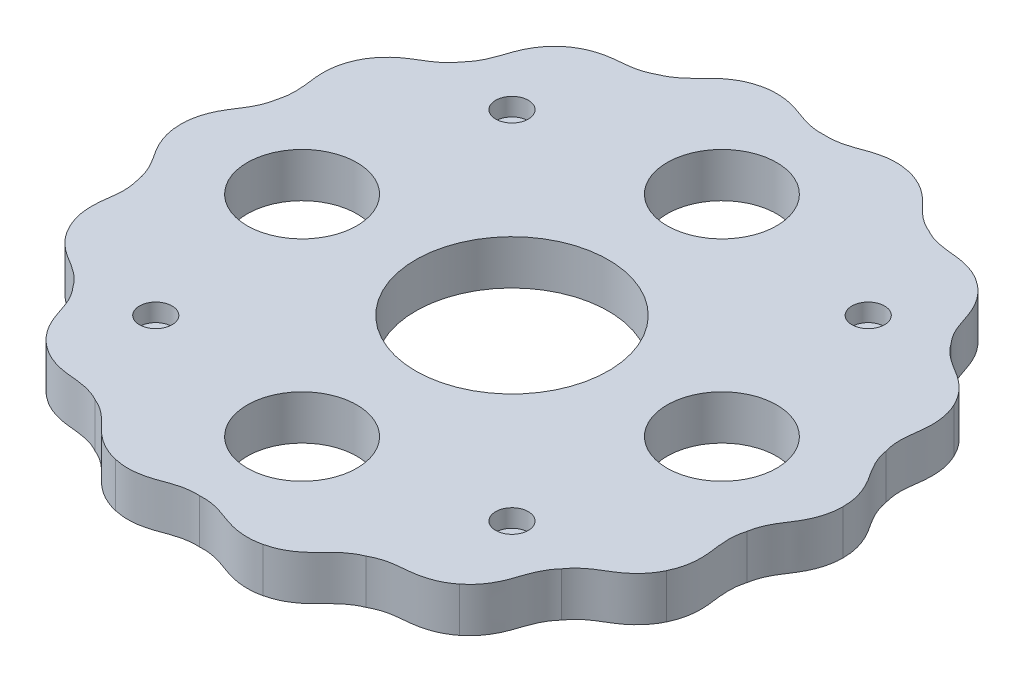
SolidWorks part; units mm, degrees
ref_plane "Front Plane" through (0, 0, 0) normal (0, 0, 1) x (1, 0, 0)
ref_plane "Top Plane" through (0, 0, 0) normal (0, 1, 0) x (1, 0, 0)
ref_plane "Right Plane" through (0, 0, 0) normal (1, 0, 0) x (0, 0, -1)
sketch "Sketch1" plane through (0, 0, 0) normal (0, 1, 0) x (1, 0, 0)
  line L0 (0, 0) -> (37.5, 0) construction
  line L1 (0, 0) -> (37.4807, 1.2019) construction
  line L2 (0, 0) -> (37.423, 2.4026) construction
  line L3 (0, 0) -> (37.3267, 3.6009) construction
  line L4 (0, 0) -> (37.1921, 4.7954) construction
  line L5 (0, 0) -> (37.0193, 5.985) construction
  line L6 (0, 0) -> (36.8085, 7.1684) construction
  line L7 (0, 0) -> (36.5598, 8.3445) construction
  line L8 (0, 0) -> (36.2736, 9.512) construction
  line L9 (0, 0) -> (35.95, 10.6698) construction
  line L10 (0, 0) -> (35.5896, 11.8166) construction
  line L11 (0, 0) -> (35.1926, 12.9512) construction
  line L12 (0, 0) -> (34.7594, 14.0725) construction
  line L13 (0, 0) -> (34.2905, 15.1794) construction
  line L14 (0, 0) -> (33.7863, 16.2706) construction
  line L15 (37.5, 0) -> (38.5, 0) construction
  line L16 (37.4807, 1.2019) -> (38.3521, 1.6927) construction
  line L17 (37.423, 2.4026) -> (37.9413, 3.2578) construction
  line L18 (37.3267, 3.6009) -> (37.3588, 4.6003) construction
  line L19 (37.1921, 4.7954) -> (36.7296, 5.682) construction
  line L20 (37.0193, 5.985) -> (36.1812, 6.5305) construction
  line L21 (36.8085, 7.1684) -> (35.8105, 7.2325) construction
  line L22 (36.5598, 8.3445) -> (35.5849, 8.122) construction
  line L23 (37, 0.0019) -> (37, 0)
  line L24 (33.3367, 16.052) -> (33.3358, 16.0537)
  line L25 (37, -0.0019) -> (37, 0)
  line L26 (33.3367, -16.052) -> (33.3358, -16.0537)
  line L27 (33.335, -16.0554) -> (33.3358, -16.0537)
  line L28 (23.0706, -28.9266) -> (23.0691, -28.9278)
  line L29 (23.0677, -28.9289) -> (23.0691, -28.9278)
  line L30 (8.2351, -36.0719) -> (8.2333, -36.0723)
  line L31 (8.2315, -36.0727) -> (8.2333, -36.0723)
  line L32 (-8.2315, -36.0727) -> (-8.2333, -36.0723)
  line L33 (-8.2351, -36.0719) -> (-8.2333, -36.0723)
  line L34 (-23.0677, -28.9289) -> (-23.0691, -28.9278)
  line L35 (-23.0706, -28.9266) -> (-23.0691, -28.9278)
  line L36 (-33.335, -16.0554) -> (-33.3358, -16.0537)
  line L37 (-33.3367, -16.052) -> (-33.3358, -16.0537)
  line L38 (-37, -0.0019) -> (-37, 0)
  line L39 (-37, 0.0019) -> (-37, 0)
  line L40 (-33.3367, 16.052) -> (-33.3358, 16.0537)
  line L41 (-33.335, 16.0554) -> (-33.3358, 16.0537)
  line L42 (-23.0706, 28.9266) -> (-23.0691, 28.9278)
  line L43 (-23.0677, 28.9289) -> (-23.0691, 28.9278)
  line L44 (-8.2351, 36.0719) -> (-8.2333, 36.0723)
  line L45 (-8.2315, 36.0727) -> (-8.2333, 36.0723)
  line L46 (8.2315, 36.0727) -> (8.2333, 36.0723)
  line L47 (8.2351, 36.0719) -> (8.2333, 36.0723)
  line L48 (23.0677, 28.9289) -> (23.0691, 28.9278)
  line L49 (23.0706, 28.9266) -> (23.0691, 28.9278)
  line L50 (33.335, 16.0554) -> (33.3358, 16.0537)
  line L51 (35.5, 0.0037) -> (35.5, 0)
  line L52 (31.986, 15.3995) -> (31.9844, 15.4029)
  line L53 (35.5, -0.0037) -> (35.5, 0)
  line L54 (31.986, -15.3995) -> (31.9844, -15.4029)
  line L55 (31.9828, -15.4062) -> (31.9844, -15.4029)
  line L56 (22.1368, -27.7527) -> (22.1339, -27.755)
  line L57 (22.131, -27.7573) -> (22.1339, -27.755)
  line L58 (7.9031, -34.6091) -> (7.8995, -34.6099)
  line L59 (7.8959, -34.6108) -> (7.8995, -34.6099)
  line L60 (-7.8959, -34.6108) -> (-7.8995, -34.6099)
  line L61 (-7.9031, -34.6091) -> (-7.8995, -34.6099)
  line L62 (-22.131, -27.7573) -> (-22.1339, -27.755)
  line L63 (-22.1368, -27.7527) -> (-22.1339, -27.755)
  line L64 (-31.9828, -15.4062) -> (-31.9844, -15.4029)
  line L65 (-31.986, -15.3995) -> (-31.9844, -15.4029)
  line L66 (-35.5, -0.0037) -> (-35.5, 0)
  line L67 (-35.5, 0.0037) -> (-35.5, 0)
  line L68 (-31.986, 15.3995) -> (-31.9844, 15.4029)
  line L69 (-31.9828, 15.4062) -> (-31.9844, 15.4029)
  line L70 (-22.1368, 27.7527) -> (-22.1339, 27.755)
  line L71 (-22.131, 27.7573) -> (-22.1339, 27.755)
  line L72 (-7.9031, 34.6091) -> (-7.8995, 34.6099)
  line L73 (-7.8959, 34.6108) -> (-7.8995, 34.6099)
  line L74 (7.8959, 34.6108) -> (7.8995, 34.6099)
  line L75 (7.9031, 34.6091) -> (7.8995, 34.6099)
  line L76 (22.131, 27.7573) -> (22.1339, 27.755)
  line L77 (22.1368, 27.7527) -> (22.1339, 27.755)
  line L78 (31.9828, 15.4062) -> (31.9844, 15.4029)
  circle A0 centre (0, 0) radius 35 construction
  circle A1 centre (37.5, 0) radius 2.5 construction
  circle A2 centre (0, 0) radius 37.5 construction
  spline S0 degree 3 poles (35.5849, 8.122) (35.6266, 7.5364) (36.0345, 6.7125) (36.7836, 5.6218) (37.4152, 4.5501) (38.2239, 2.702) (38.5014, 1.1074) (38.5, 0) knots 0 0 0 0 0.195516 0.310928 0.453873 0.621058 1 1 1 1
  spline S1 degree 3 poles (35.5849, 8.122) (35.3683, 8.6678) (35.3784, 9.5871) (35.5801, 10.8948) (35.6841, 12.1344) (35.611, 14.1503) (35.169, 15.7074) (34.6873, 16.7045) knots 0 0 0 0 0.195516 0.310928 0.453873 0.621058 1 1 1 1
  spline S2 degree 1 poles (34.1119, 7.7858) (33.3367, 16.052) knots 0 0 1 1 construction
  spline S3 degree 1 poles (34.1119, 7.7858) (37, 0.0019) knots 0 0 1 1 construction
  spline S4 degree 3 poles (33.3367, 16.052) (33.6005, 15.5058) (33.9037, 14.6401) (34.1146, 13.4372) (34.174, 12.5211) (34.1413, 11.5771) (34.0239, 10.6392) (33.8823, 9.6155) (33.9055, 8.625) (34.0243, 8.0514) (34.1119, 7.7858) knots 0.015853 0.015853 0.015853 0.015853 0.26189 0.384908 0.507927 0.630945 0.753963 0.876982 0.938491 1 1 1 1
  spline S5 degree 3 poles (34.1119, 7.7858) (34.1483, 7.5085) (34.2901, 6.9402) (34.6989, 6.0377) (35.2706, 5.1769) (35.7834, 4.3828) (36.2224, 3.5464) (36.5664, 2.6953) (36.8983, 1.52) (37.0008, 0.6085) (37, 0.0019) knots 0.015853 0.015853 0.015853 0.015853 0.077362 0.138872 0.26189 0.384908 0.507927 0.630945 0.753963 1 1 1 1
  spline S6 degree 3 poles (37, -0.0019) (37.0008, -0.6085) (36.8983, -1.52) (36.5664, -2.6953) (36.2224, -3.5464) (35.7834, -4.3828) (35.2706, -5.1769) (34.6989, -6.0377) (34.2901, -6.9402) (34.1483, -7.5085) (34.1119, -7.7858) knots 0.015853 0.015853 0.015853 0.015853 0.26189 0.384908 0.507927 0.630945 0.753963 0.876982 0.938491 1 1 1 1
  spline S7 degree 3 poles (34.1119, -7.7858) (34.0243, -8.0514) (33.9055, -8.625) (33.8823, -9.6155) (34.0239, -10.6392) (34.1413, -11.5771) (34.174, -12.5211) (34.1146, -13.4372) (33.9037, -14.6401) (33.6005, -15.5058) (33.3367, -16.052) knots 0.015853 0.015853 0.015853 0.015853 0.077362 0.138872 0.26189 0.384908 0.507927 0.630945 0.753963 1 1 1 1
  spline S8 degree 3 poles (33.335, -16.0554) (33.0725, -16.6022) (32.5847, -17.3791) (31.7758, -18.2939) (31.0965, -18.9115) (30.3381, -19.4746) (29.5316, -19.9675) (28.6429, -20.4951) (27.8831, -21.1308) (27.5087, -21.5813) (27.3556, -21.8154) knots 0.015853 0.015853 0.015853 0.015853 0.26189 0.384908 0.507927 0.630945 0.753963 0.876982 0.938491 1 1 1 1
  spline S9 degree 3 poles (27.3556, -21.8154) (27.1615, -22.0167) (26.8056, -22.4819) (26.3549, -23.3642) (26.0383, -24.348) (25.7371, -25.2439) (25.357, -26.1087) (24.906, -26.9083) (24.1941, -27.9005) (23.5453, -28.549) (23.0706, -28.9266) knots 0.015853 0.015853 0.015853 0.015853 0.077362 0.138872 0.26189 0.384908 0.507927 0.630945 0.753963 1 1 1 1
  spline S10 degree 3 poles (23.0677, -28.9289) (22.5939, -29.3077) (21.8173, -29.796) (20.6915, -30.2693) (19.8116, -30.531) (18.884, -30.7092) (17.9435, -30.8034) (16.9139, -30.8931) (15.9535, -31.1362) (15.4207, -31.3797) (15.1812, -31.5241) knots 0.015853 0.015853 0.015853 0.015853 0.26189 0.384908 0.507927 0.630945 0.753963 0.876982 0.938491 1 1 1 1
  spline S11 degree 3 poles (15.1812, -31.5241) (14.919, -31.6213) (14.3964, -31.886) (13.6076, -32.4854) (12.8955, -33.2344) (12.2354, -33.9109) (11.5177, -34.5251) (10.7645, -35.0499) (9.6926, -35.6349) (8.8266, -35.9377) (8.2351, -36.0719) knots 0.015853 0.015853 0.015853 0.015853 0.077362 0.138872 0.26189 0.384908 0.507927 0.630945 0.753963 1 1 1 1
  spline S12 degree 3 poles (8.2315, -36.0727) (7.6402, -36.2085) (6.7287, -36.3114) (5.5091, -36.2494) (4.6028, -36.1034) (3.6897, -35.8614) (2.8014, -35.5383) (1.8349, -35.1724) (0.8641, -34.9747) (0.2785, -34.9629) (0, -34.9891) knots 0.015853 0.015853 0.015853 0.015853 0.26189 0.384908 0.507927 0.630945 0.753963 0.876982 0.938491 1 1 1 1
  spline S13 degree 3 poles (0, -34.9891) (-0.2785, -34.9629) (-0.8641, -34.9747) (-1.8349, -35.1724) (-2.8014, -35.5383) (-3.6897, -35.8614) (-4.6028, -36.1034) (-5.5091, -36.2494) (-6.7287, -36.3114) (-7.6402, -36.2085) (-8.2315, -36.0727) knots 0.015853 0.015853 0.015853 0.015853 0.077362 0.138872 0.26189 0.384908 0.507927 0.630945 0.753963 1 1 1 1
  spline S14 degree 3 poles (-8.2351, -36.0719) (-8.8266, -35.9377) (-9.6926, -35.6349) (-10.7645, -35.0499) (-11.5177, -34.5251) (-12.2354, -33.9109) (-12.8955, -33.2344) (-13.6076, -32.4854) (-14.3964, -31.886) (-14.919, -31.6213) (-15.1812, -31.5241) knots 0.015853 0.015853 0.015853 0.015853 0.26189 0.384908 0.507927 0.630945 0.753963 0.876982 0.938491 1 1 1 1
  spline S15 degree 3 poles (-15.1812, -31.5241) (-15.4207, -31.3797) (-15.9535, -31.1362) (-16.9139, -30.8931) (-17.9435, -30.8034) (-18.884, -30.7092) (-19.8116, -30.531) (-20.6915, -30.2693) (-21.8173, -29.796) (-22.5939, -29.3077) (-23.0677, -28.9289) knots 0.015853 0.015853 0.015853 0.015853 0.077362 0.138872 0.26189 0.384908 0.507927 0.630945 0.753963 1 1 1 1
  spline S16 degree 3 poles (-23.0706, -28.9266) (-23.5453, -28.549) (-24.1941, -27.9005) (-24.906, -26.9083) (-25.357, -26.1087) (-25.7371, -25.2439) (-26.0383, -24.348) (-26.3549, -23.3642) (-26.8056, -22.4819) (-27.1615, -22.0167) (-27.3556, -21.8154) knots 0.015853 0.015853 0.015853 0.015853 0.26189 0.384908 0.507927 0.630945 0.753963 0.876982 0.938491 1 1 1 1
  spline S17 degree 3 poles (-27.3556, -21.8154) (-27.5087, -21.5813) (-27.8831, -21.1308) (-28.6429, -20.4951) (-29.5316, -19.9675) (-30.3381, -19.4746) (-31.0965, -18.9115) (-31.7758, -18.2939) (-32.5847, -17.3791) (-33.0725, -16.6022) (-33.335, -16.0554) knots 0.015853 0.015853 0.015853 0.015853 0.077362 0.138872 0.26189 0.384908 0.507927 0.630945 0.753963 1 1 1 1
  spline S18 degree 3 poles (-33.3367, -16.052) (-33.6005, -15.5058) (-33.9037, -14.6401) (-34.1146, -13.4372) (-34.174, -12.5211) (-34.1413, -11.5771) (-34.0239, -10.6392) (-33.8823, -9.6155) (-33.9055, -8.625) (-34.0243, -8.0514) (-34.1119, -7.7858) knots 0.015853 0.015853 0.015853 0.015853 0.26189 0.384908 0.507927 0.630945 0.753963 0.876982 0.938491 1 1 1 1
  spline S19 degree 3 poles (-34.1119, -7.7858) (-34.1483, -7.5085) (-34.2901, -6.9402) (-34.6989, -6.0377) (-35.2706, -5.1769) (-35.7834, -4.3828) (-36.2224, -3.5464) (-36.5664, -2.6953) (-36.8983, -1.52) (-37.0008, -0.6085) (-37, -0.0019) knots 0.015853 0.015853 0.015853 0.015853 0.077362 0.138872 0.26189 0.384908 0.507927 0.630945 0.753963 1 1 1 1
  spline S20 degree 3 poles (-37, 0.0019) (-37.0008, 0.6085) (-36.8983, 1.52) (-36.5664, 2.6953) (-36.2224, 3.5464) (-35.7834, 4.3828) (-35.2706, 5.1769) (-34.6989, 6.0377) (-34.2901, 6.9402) (-34.1483, 7.5085) (-34.1119, 7.7858) knots 0.015853 0.015853 0.015853 0.015853 0.26189 0.384908 0.507927 0.630945 0.753963 0.876982 0.938491 1 1 1 1
  spline S21 degree 3 poles (-34.1119, 7.7858) (-34.0243, 8.0514) (-33.9055, 8.625) (-33.8823, 9.6155) (-34.0239, 10.6392) (-34.1413, 11.5771) (-34.174, 12.5211) (-34.1146, 13.4372) (-33.9037, 14.6401) (-33.6005, 15.5058) (-33.3367, 16.052) knots 0.015853 0.015853 0.015853 0.015853 0.077362 0.138872 0.26189 0.384908 0.507927 0.630945 0.753963 1 1 1 1
  spline S22 degree 3 poles (-33.335, 16.0554) (-33.0725, 16.6022) (-32.5847, 17.3791) (-31.7758, 18.2939) (-31.0965, 18.9115) (-30.3381, 19.4746) (-29.5316, 19.9675) (-28.6429, 20.4951) (-27.8831, 21.1308) (-27.5087, 21.5813) (-27.3556, 21.8154) knots 0.015853 0.015853 0.015853 0.015853 0.26189 0.384908 0.507927 0.630945 0.753963 0.876982 0.938491 1 1 1 1
  spline S23 degree 3 poles (-27.3556, 21.8154) (-27.1615, 22.0167) (-26.8056, 22.4819) (-26.3549, 23.3642) (-26.0383, 24.348) (-25.7371, 25.2439) (-25.357, 26.1087) (-24.906, 26.9083) (-24.1941, 27.9005) (-23.5453, 28.549) (-23.0706, 28.9266) knots 0.015853 0.015853 0.015853 0.015853 0.077362 0.138872 0.26189 0.384908 0.507927 0.630945 0.753963 1 1 1 1
  spline S24 degree 3 poles (-23.0677, 28.9289) (-22.5939, 29.3077) (-21.8173, 29.796) (-20.6915, 30.2693) (-19.8116, 30.531) (-18.884, 30.7092) (-17.9435, 30.8034) (-16.9139, 30.8931) (-15.9535, 31.1362) (-15.4207, 31.3797) (-15.1812, 31.5241) knots 0.015853 0.015853 0.015853 0.015853 0.26189 0.384908 0.507927 0.630945 0.753963 0.876982 0.938491 1 1 1 1
  spline S25 degree 3 poles (-15.1812, 31.5241) (-14.919, 31.6213) (-14.3964, 31.886) (-13.6076, 32.4854) (-12.8955, 33.2344) (-12.2354, 33.9109) (-11.5177, 34.5251) (-10.7645, 35.0499) (-9.6926, 35.6349) (-8.8266, 35.9377) (-8.2351, 36.0719) knots 0.015853 0.015853 0.015853 0.015853 0.077362 0.138872 0.26189 0.384908 0.507927 0.630945 0.753963 1 1 1 1
  spline S26 degree 3 poles (-8.2315, 36.0727) (-7.6402, 36.2085) (-6.7287, 36.3114) (-5.5091, 36.2494) (-4.6028, 36.1034) (-3.6897, 35.8614) (-2.8014, 35.5383) (-1.8349, 35.1724) (-0.8641, 34.9747) (-0.2785, 34.9629) (0, 34.9891) knots 0.015853 0.015853 0.015853 0.015853 0.26189 0.384908 0.507927 0.630945 0.753963 0.876982 0.938491 1 1 1 1
  spline S27 degree 3 poles (0, 34.9891) (0.2785, 34.9629) (0.8641, 34.9747) (1.8349, 35.1724) (2.8014, 35.5383) (3.6897, 35.8614) (4.6028, 36.1034) (5.5091, 36.2494) (6.7287, 36.3114) (7.6402, 36.2085) (8.2315, 36.0727) knots 0.015853 0.015853 0.015853 0.015853 0.077362 0.138872 0.26189 0.384908 0.507927 0.630945 0.753963 1 1 1 1
  spline S28 degree 3 poles (8.2351, 36.0719) (8.8266, 35.9377) (9.6926, 35.6349) (10.7645, 35.0499) (11.5177, 34.5251) (12.2354, 33.9109) (12.8955, 33.2344) (13.6076, 32.4854) (14.3964, 31.886) (14.919, 31.6213) (15.1812, 31.5241) knots 0.015853 0.015853 0.015853 0.015853 0.26189 0.384908 0.507927 0.630945 0.753963 0.876982 0.938491 1 1 1 1
  spline S29 degree 3 poles (15.1812, 31.5241) (15.4207, 31.3797) (15.9535, 31.1362) (16.9139, 30.8931) (17.9435, 30.8034) (18.884, 30.7092) (19.8116, 30.531) (20.6915, 30.2693) (21.8173, 29.796) (22.5939, 29.3077) (23.0677, 28.9289) knots 0.015853 0.015853 0.015853 0.015853 0.077362 0.138872 0.26189 0.384908 0.507927 0.630945 0.753963 1 1 1 1
  spline S30 degree 3 poles (23.0706, 28.9266) (23.5453, 28.549) (24.1941, 27.9005) (24.906, 26.9083) (25.357, 26.1087) (25.7371, 25.2439) (26.0383, 24.348) (26.3549, 23.3642) (26.8056, 22.4819) (27.1615, 22.0167) (27.3556, 21.8154) knots 0.015853 0.015853 0.015853 0.015853 0.26189 0.384908 0.507927 0.630945 0.753963 0.876982 0.938491 1 1 1 1
  spline S31 degree 3 poles (27.3556, 21.8154) (27.5087, 21.5813) (27.8831, 21.1308) (28.6429, 20.4951) (29.5316, 19.9675) (30.3381, 19.4746) (31.0965, 18.9115) (31.7758, 18.2939) (32.5847, 17.3791) (33.0725, 16.6022) (33.335, 16.0554) knots 0.015853 0.015853 0.015853 0.015853 0.077362 0.138872 0.26189 0.384908 0.507927 0.630945 0.753963 1 1 1 1
  spline S32 degree 1 poles (32.6448, 7.451) (35.5, 0.0037) knots 0 0 1 1 construction
  spline S33 degree 1 poles (32.6448, 7.451) (31.986, 15.3995) knots 0 0 1 1 construction
  spline S34 degree 3 poles (35.5, 0.0037) (35.5006, 0.4959) (35.4183, 1.2336) (35.1496, 2.1927) (34.8707, 2.8896) (34.4997, 3.6015) (34.1394, 4.1652) (33.6939, 4.8394) (33.3068, 5.4873) (32.9751, 6.1975) (32.758, 6.8733) (32.6748, 7.2607) (32.6448, 7.451) knots 0.023011 0.023011 0.023011 0.023011 0.267258 0.389382 0.511505 0.633629 0.755753 0.816814 0.877876 0.938938 0.969469 1 1 1 1
  spline S35 degree 3 poles (32.6448, 7.451) (32.5893, 7.6354) (32.4961, 8.0206) (32.3985, 8.7236) (32.3893, 9.5074) (32.4569, 10.2591) (32.5657, 11.0598) (32.6458, 11.724) (32.6712, 12.5264) (32.6201, 13.2752) (32.446, 14.256) (32.2001, 14.9563) (31.986, 15.3995) knots 0.023011 0.023011 0.023011 0.023011 0.053542 0.084072 0.145134 0.206196 0.267258 0.389382 0.511505 0.633629 0.755753 1 1 1 1
  spline S36 degree 3 poles (32.6448, -7.451) (32.6748, -7.2607) (32.758, -6.8733) (32.9751, -6.1975) (33.3068, -5.4873) (33.6939, -4.8394) (34.1394, -4.1652) (34.4997, -3.6015) (34.8707, -2.8896) (35.1496, -2.1927) (35.4183, -1.2336) (35.5006, -0.4959) (35.5, -0.0037) knots 0.023011 0.023011 0.023011 0.023011 0.053542 0.084072 0.145134 0.206196 0.267258 0.389382 0.511505 0.633629 0.755753 1 1 1 1
  spline S37 degree 3 poles (31.986, -15.3995) (32.2001, -14.9563) (32.446, -14.256) (32.6201, -13.2752) (32.6712, -12.5264) (32.6458, -11.724) (32.5657, -11.0598) (32.4569, -10.2591) (32.3893, -9.5074) (32.3985, -8.7236) (32.4961, -8.0206) (32.5893, -7.6354) (32.6448, -7.451) knots 0.023011 0.023011 0.023011 0.023011 0.267258 0.389382 0.511505 0.633629 0.755753 0.816814 0.877876 0.938938 0.969469 1 1 1 1
  spline S38 degree 3 poles (26.1791, -20.8771) (26.2887, -20.7187) (26.5317, -20.4057) (27.0205, -19.8911) (27.6275, -19.3952) (28.2574, -18.9793) (28.9513, -18.5652) (29.5206, -18.2137) (30.1637, -17.7333) (30.7173, -17.2264) (31.3755, -16.4789) (31.7698, -15.8499) (31.9828, -15.4062) knots 0.023011 0.023011 0.023011 0.023011 0.053542 0.084072 0.145134 0.206196 0.267258 0.389382 0.511505 0.633629 0.755753 1 1 1 1
  spline S39 degree 3 poles (22.1368, -27.7527) (22.522, -27.4463) (23.0474, -26.922) (23.6297, -26.1139) (24.0007, -25.4614) (24.326, -24.7275) (24.542, -24.0943) (24.7914, -23.3257) (25.0566, -22.619) (25.405, -21.9169) (25.798, -21.3258) (26.0491, -21.0192) (26.1791, -20.8771) knots 0.023011 0.023011 0.023011 0.023011 0.267258 0.389382 0.511505 0.633629 0.755753 0.816814 0.877876 0.938938 0.969469 1 1 1 1
  spline S40 degree 3 poles (14.5283, -30.1683) (14.6957, -30.0732) (15.0505, -29.8966) (15.7143, -29.645) (16.4763, -29.4616) (17.2242, -29.3602) (18.0291, -29.2882) (18.6945, -29.2185) (19.4823, -29.0647) (20.201, -28.8482) (21.1184, -28.4603) (21.7465, -28.0647) (22.131, -27.7573) knots 0.023011 0.023011 0.023011 0.023011 0.053542 0.084072 0.145134 0.206196 0.267258 0.389382 0.511505 0.633629 0.755753 1 1 1 1
  spline S41 degree 3 poles (7.9031, -34.6091) (8.3831, -34.5002) (9.084, -34.2557) (9.9593, -33.7804) (10.5766, -33.3534) (11.1881, -32.8334) (11.6575, -32.3566) (12.2156, -31.7723) (12.7612, -31.2507) (13.3797, -30.7693) (13.9903, -30.4072) (14.3495, -30.2399) (14.5283, -30.1683) knots 0.023011 0.023011 0.023011 0.023011 0.267258 0.389382 0.511505 0.633629 0.755753 0.816814 0.877876 0.938938 0.969469 1 1 1 1
  spline S42 degree 3 poles (0, -33.4843) (0.1922, -33.4712) (0.5884, -33.4661) (1.2956, -33.5274) (2.0617, -33.6928) (2.7796, -33.926) (3.536, -34.2103) (4.1657, -34.4362) (4.9423, -34.6394) (5.6838, -34.7562) (6.6786, -34.8048) (7.4161, -34.7209) (7.8959, -34.6108) knots 0.023011 0.023011 0.023011 0.023011 0.053542 0.084072 0.145134 0.206196 0.267258 0.389382 0.511505 0.633629 0.755753 1 1 1 1
  spline S43 degree 3 poles (-7.8959, -34.6108) (-7.4161, -34.7209) (-6.6786, -34.8048) (-5.6838, -34.7562) (-4.9423, -34.6394) (-4.1657, -34.4362) (-3.536, -34.2103) (-2.7796, -33.926) (-2.0617, -33.6928) (-1.2956, -33.5274) (-0.5884, -33.4661) (-0.1922, -33.4712) (0, -33.4843) knots 0.023011 0.023011 0.023011 0.023011 0.267258 0.389382 0.511505 0.633629 0.755753 0.816814 0.877876 0.938938 0.969469 1 1 1 1
  spline S44 degree 3 poles (-14.5283, -30.1683) (-14.3495, -30.2399) (-13.9903, -30.4072) (-13.3797, -30.7693) (-12.7612, -31.2507) (-12.2156, -31.7723) (-11.6575, -32.3566) (-11.1881, -32.8334) (-10.5766, -33.3534) (-9.9593, -33.7804) (-9.084, -34.2557) (-8.3831, -34.5002) (-7.9031, -34.6091) knots 0.023011 0.023011 0.023011 0.023011 0.053542 0.084072 0.145134 0.206196 0.267258 0.389382 0.511505 0.633629 0.755753 1 1 1 1
  spline S45 degree 3 poles (-22.131, -27.7573) (-21.7465, -28.0647) (-21.1184, -28.4603) (-20.201, -28.8482) (-19.4823, -29.0647) (-18.6945, -29.2185) (-18.0291, -29.2882) (-17.2242, -29.3602) (-16.4763, -29.4616) (-15.7143, -29.645) (-15.0505, -29.8966) (-14.6957, -30.0732) (-14.5283, -30.1683) knots 0.023011 0.023011 0.023011 0.023011 0.267258 0.389382 0.511505 0.633629 0.755753 0.816814 0.877876 0.938938 0.969469 1 1 1 1
  spline S46 degree 3 poles (-26.1791, -20.8771) (-26.0491, -21.0192) (-25.798, -21.3258) (-25.405, -21.9169) (-25.0566, -22.619) (-24.7914, -23.3257) (-24.542, -24.0943) (-24.326, -24.7275) (-24.0007, -25.4614) (-23.6297, -26.1139) (-23.0474, -26.922) (-22.522, -27.4463) (-22.1368, -27.7527) knots 0.023011 0.023011 0.023011 0.023011 0.053542 0.084072 0.145134 0.206196 0.267258 0.389382 0.511505 0.633629 0.755753 1 1 1 1
  spline S47 degree 3 poles (-31.9828, -15.4062) (-31.7698, -15.8499) (-31.3755, -16.4789) (-30.7173, -17.2264) (-30.1637, -17.7333) (-29.5206, -18.2137) (-28.9513, -18.5652) (-28.2574, -18.9793) (-27.6275, -19.3952) (-27.0205, -19.8911) (-26.5317, -20.4057) (-26.2887, -20.7187) (-26.1791, -20.8771) knots 0.023011 0.023011 0.023011 0.023011 0.267258 0.389382 0.511505 0.633629 0.755753 0.816814 0.877876 0.938938 0.969469 1 1 1 1
  spline S48 degree 3 poles (-32.6448, -7.451) (-32.5893, -7.6354) (-32.4961, -8.0206) (-32.3985, -8.7236) (-32.3893, -9.5074) (-32.4569, -10.2591) (-32.5657, -11.0598) (-32.6458, -11.724) (-32.6712, -12.5264) (-32.6201, -13.2752) (-32.446, -14.256) (-32.2001, -14.9563) (-31.986, -15.3995) knots 0.023011 0.023011 0.023011 0.023011 0.053542 0.084072 0.145134 0.206196 0.267258 0.389382 0.511505 0.633629 0.755753 1 1 1 1
  spline S49 degree 3 poles (-35.5, -0.0037) (-35.5006, -0.4959) (-35.4183, -1.2336) (-35.1496, -2.1927) (-34.8707, -2.8896) (-34.4997, -3.6015) (-34.1394, -4.1652) (-33.6939, -4.8394) (-33.3068, -5.4873) (-32.9751, -6.1975) (-32.758, -6.8733) (-32.6748, -7.2607) (-32.6448, -7.451) knots 0.023011 0.023011 0.023011 0.023011 0.267258 0.389382 0.511505 0.633629 0.755753 0.816814 0.877876 0.938938 0.969469 1 1 1 1
  spline S50 degree 3 poles (-32.6448, 7.451) (-32.6748, 7.2607) (-32.758, 6.8733) (-32.9751, 6.1975) (-33.3068, 5.4873) (-33.6939, 4.8394) (-34.1394, 4.1652) (-34.4997, 3.6015) (-34.8707, 2.8896) (-35.1496, 2.1927) (-35.4183, 1.2336) (-35.5006, 0.4959) (-35.5, 0.0037) knots 0.023011 0.023011 0.023011 0.023011 0.053542 0.084072 0.145134 0.206196 0.267258 0.389382 0.511505 0.633629 0.755753 1 1 1 1
  spline S51 degree 3 poles (-31.986, 15.3995) (-32.2001, 14.9563) (-32.446, 14.256) (-32.6201, 13.2752) (-32.6712, 12.5264) (-32.6458, 11.724) (-32.5657, 11.0598) (-32.4569, 10.2591) (-32.3893, 9.5074) (-32.3985, 8.7236) (-32.4961, 8.0206) (-32.5893, 7.6354) (-32.6448, 7.451) knots 0.023011 0.023011 0.023011 0.023011 0.267258 0.389382 0.511505 0.633629 0.755753 0.816814 0.877876 0.938938 0.969469 1 1 1 1
  spline S52 degree 3 poles (-26.1791, 20.8771) (-26.2887, 20.7187) (-26.5317, 20.4057) (-27.0205, 19.8911) (-27.6275, 19.3952) (-28.2574, 18.9793) (-28.9513, 18.5652) (-29.5206, 18.2137) (-30.1637, 17.7333) (-30.7173, 17.2264) (-31.3755, 16.4789) (-31.7698, 15.8499) (-31.9828, 15.4062) knots 0.023011 0.023011 0.023011 0.023011 0.053542 0.084072 0.145134 0.206196 0.267258 0.389382 0.511505 0.633629 0.755753 1 1 1 1
  spline S53 degree 3 poles (-22.1368, 27.7527) (-22.522, 27.4463) (-23.0474, 26.922) (-23.6297, 26.1139) (-24.0007, 25.4614) (-24.326, 24.7275) (-24.542, 24.0943) (-24.7914, 23.3257) (-25.0566, 22.619) (-25.405, 21.9169) (-25.798, 21.3258) (-26.0491, 21.0192) (-26.1791, 20.8771) knots 0.023011 0.023011 0.023011 0.023011 0.267258 0.389382 0.511505 0.633629 0.755753 0.816814 0.877876 0.938938 0.969469 1 1 1 1
  spline S54 degree 3 poles (-14.5283, 30.1683) (-14.6957, 30.0732) (-15.0505, 29.8966) (-15.7143, 29.645) (-16.4763, 29.4616) (-17.2242, 29.3602) (-18.0291, 29.2882) (-18.6945, 29.2185) (-19.4823, 29.0647) (-20.201, 28.8482) (-21.1184, 28.4603) (-21.7465, 28.0647) (-22.131, 27.7573) knots 0.023011 0.023011 0.023011 0.023011 0.053542 0.084072 0.145134 0.206196 0.267258 0.389382 0.511505 0.633629 0.755753 1 1 1 1
  spline S55 degree 3 poles (-7.9031, 34.6091) (-8.3831, 34.5002) (-9.084, 34.2557) (-9.9593, 33.7804) (-10.5766, 33.3534) (-11.1881, 32.8334) (-11.6575, 32.3566) (-12.2156, 31.7723) (-12.7612, 31.2507) (-13.3797, 30.7693) (-13.9903, 30.4072) (-14.3495, 30.2399) (-14.5283, 30.1683) knots 0.023011 0.023011 0.023011 0.023011 0.267258 0.389382 0.511505 0.633629 0.755753 0.816814 0.877876 0.938938 0.969469 1 1 1 1
  spline S56 degree 3 poles (0, 33.4843) (-0.1922, 33.4712) (-0.5884, 33.4661) (-1.2956, 33.5274) (-2.0617, 33.6928) (-2.7796, 33.926) (-3.536, 34.2103) (-4.1657, 34.4362) (-4.9423, 34.6394) (-5.6838, 34.7562) (-6.6786, 34.8048) (-7.4161, 34.7209) (-7.8959, 34.6108) knots 0.023011 0.023011 0.023011 0.023011 0.053542 0.084072 0.145134 0.206196 0.267258 0.389382 0.511505 0.633629 0.755753 1 1 1 1
  spline S57 degree 3 poles (7.8959, 34.6108) (7.4161, 34.7209) (6.6786, 34.8048) (5.6838, 34.7562) (4.9423, 34.6394) (4.1657, 34.4362) (3.536, 34.2103) (2.7796, 33.926) (2.0617, 33.6928) (1.2956, 33.5274) (0.5884, 33.4661) (0.1922, 33.4712) (0, 33.4843) knots 0.023011 0.023011 0.023011 0.023011 0.267258 0.389382 0.511505 0.633629 0.755753 0.816814 0.877876 0.938938 0.969469 1 1 1 1
  spline S58 degree 3 poles (14.5283, 30.1683) (14.3495, 30.2399) (13.9903, 30.4072) (13.3797, 30.7693) (12.7612, 31.2507) (12.2156, 31.7723) (11.6575, 32.3566) (11.1881, 32.8334) (10.5766, 33.3534) (9.9593, 33.7804) (9.084, 34.2557) (8.3831, 34.5002) (7.9031, 34.6091) knots 0.023011 0.023011 0.023011 0.023011 0.053542 0.084072 0.145134 0.206196 0.267258 0.389382 0.511505 0.633629 0.755753 1 1 1 1
  spline S59 degree 3 poles (22.131, 27.7573) (21.7465, 28.0647) (21.1184, 28.4603) (20.201, 28.8482) (19.4823, 29.0647) (18.6945, 29.2185) (18.0291, 29.2882) (17.2242, 29.3602) (16.4763, 29.4616) (15.7143, 29.645) (15.0505, 29.8966) (14.6957, 30.0732) (14.5283, 30.1683) knots 0.023011 0.023011 0.023011 0.023011 0.267258 0.389382 0.511505 0.633629 0.755753 0.816814 0.877876 0.938938 0.969469 1 1 1 1
  spline S60 degree 3 poles (26.1791, 20.8771) (26.0491, 21.0192) (25.798, 21.3258) (25.405, 21.9169) (25.0566, 22.619) (24.7914, 23.3257) (24.542, 24.0943) (24.326, 24.7275) (24.0007, 25.4614) (23.6297, 26.1139) (23.0474, 26.922) (22.522, 27.4463) (22.1368, 27.7527) knots 0.023011 0.023011 0.023011 0.023011 0.053542 0.084072 0.145134 0.206196 0.267258 0.389382 0.511505 0.633629 0.755753 1 1 1 1
  spline S61 degree 3 poles (31.9828, 15.4062) (31.7698, 15.8499) (31.3755, 16.4789) (30.7173, 17.2264) (30.1637, 17.7333) (29.5206, 18.2137) (28.9513, 18.5652) (28.2574, 18.9793) (27.6275, 19.3952) (27.0205, 19.8911) (26.5317, 20.4057) (26.2887, 20.7187) (26.1791, 20.8771) knots 0.023011 0.023011 0.023011 0.023011 0.267258 0.389382 0.511505 0.633629 0.755753 0.816814 0.877876 0.938938 0.969469 1 1 1 1
  point P25 (0, 0)
  point P117 (0, 0)
  point P174 (0, 0)
  dimension "D1" = 70
  dimension "D2" = 5
  dimension "D4" = 25.714
  dimension "D5" = 1
  dimension "D7" = 180
  dimension "D8" = 207.551
  dimension "D6" = 1
  dimension "D9" = 1
  dimension "D10" = 235.102
  dimension "D11" = 1
  dimension "D12" = 1
  dimension "D13" = 1
  dimension "D14" = 1
  dimension "D15" = 1
  dimension "D16" = 262.653
  dimension "D17" = 290.204
  dimension "D18" = 317.755
  dimension "D19" = 345.306
  dimension "D20" = 1.5
  dimension "D22" = 3
  dimension "D3" = 15
  dimension "D21" = 14
  dimension "D23" = 14
extrude "Boss-Extrude3" add sketch "Sketch1" along normal blind 4.7625 contours L51 L53 S36 S37 L54 L55 S38 S39 L56 L57 S40 S41 L58 L59 S42 S43 L60 L61 S44 S45 L62 L63 S46 S47 L64 L65 S48 S49 L66 L67 S50 S51 L68 L69 S52 S53 L70 L71 S54 S55 L72 L73 S56 S57 L74 L75 S58 S59 L76 L77 S60 S61 L78 L52 S35 S34
sketch "Sketch2" plane through (0, 4.7625, 0) normal (0, 1, 0) x (1, 0, 0)
  line L0 (0, 0) -> (22.5, 0) construction
  line L1 (0, 0) -> (19.0919, 19.0919) construction
  circle A0 centre (0, 0) radius 10.3281
  circle A1 centre (22.5, 0) radius 5.875
  circle A6 centre (19.0919, 19.0919) radius 1.75
  circle A7 centre (0, -22.5) radius 5.875
  circle A8 centre (19.0919, -19.0919) radius 1.75
  circle A9 centre (-22.5, 0) radius 5.875
  circle A10 centre (-19.0919, -19.0919) radius 1.75
  circle A11 centre (0, 22.5) radius 5.875
  circle A12 centre (-19.0919, 19.0919) radius 1.75
  point P16 (0, 0)
  point P21 (0, 0)
  point P24 (0, 0)
  dimension "D3" = 11.75
  dimension "D1" = 20.6562
  dimension "D6" = 3.5
  dimension "D2" = 22.5
  dimension "D4" = 45
  dimension "D5" = 27
  dimension "D7" = 4
extrude "Cut-Extrude1" cut sketch "Sketch2" against normal blind 4.7625 contours A7 | A0 | A0 | A0 | L0 A0 | A0 L0 | A1 | A9 | A11 region at (0, 4.7625, 0) region at (22.5, 4.7625, 0) region at (0, 4.7625, 22.5) region at (-22.5, 4.7625, 0) region at (0, 4.7625, -22.5)
extrude "Cut-Extrude2" cut sketch "Sketch2<4>" against normal blind 1.9125 contours A12 | A10 | A8 | A6 region at (19.0919, 4.7625, -19.0919) region at (19.0919, 4.7625, 19.0919) region at (-19.0919, 4.7625, 19.0919) region at (-19.0919, 4.7625, -19.0919)
sketch "Sketch2<4>" plane through (0, 4.7625, 0) normal (0, 1, 0) x (1, 0, 0) same geometry as "Sketch2"
equation "\"D5@Sketch1\" = \"eccentricity\""
equation "\"D6@Sketch1\" = \"eccentricity\""
equation "\"D9@Sketch1\" = \"eccentricity\""
equation "\"D11@Sketch1\" = \"eccentricity\""
equation "\"D12@Sketch1\" = \"eccentricity\""
equation "\"D14@Sketch1\" = \"eccentricity\""
equation "\"D13@Sketch1\" = \"eccentricity\""
equation "\"D15@Sketch1\"= \"eccentricity\""
equation "\"D1@Sketch2\"=\"largeBearOD\"-\"largeBearOTight\""
equation "\"D1@Cut-Extrude2\"=\"ballBearDiam\"-\"sheetThickness\"/3"
equation "\"D1@Boss-Extrude3\"=\"sheetThickness\""
equation "\"smallBearOD\"= 14.8mm"
equation "\"smallBearID\" = 10mm"
equation "\"smallBearOTight\"= 0mm'calibrate - hold onto bottom of gearbox"
equation "\"smallBearOLoose\"= 0mm'calibrate - able to take off topHat"
equation "\"smallBearITight\" = 0mm'hold onto "
equation "\"pinCircleDiam\"= 75mm"
equation "\"pinDiam\"= 6mm"
equation "\"sheetThickness\"= 0.1875in"
equation "\"D6@Sketch2\"=\"ballBearDiam\""
equation "\"largeBearOD\"= 21mm"
equation "\"largeBearID\" = 15mm"
equation "\"largeBearOTight\"= 0.34375mm'calibrate - hold onto gears"
equation "\"largeBearITight\"= 0mm'calibrate - hold onto eccentric nut"
equation "\"ballBearDiam\"= 3.5mm"
equation "\"thrustBearingThickness\"= 5mm'measure this irl and change"
equation "\"thrustBearingID\"= 0mm'measure this irl and change"
equation "\"thrustBearingOD\"= 0mm'measure this irl and change"
equation "\"eccentricity\" = 1mm"
equation "\"D1@Cut-Extrude1\"=\"sheetThickness\""
